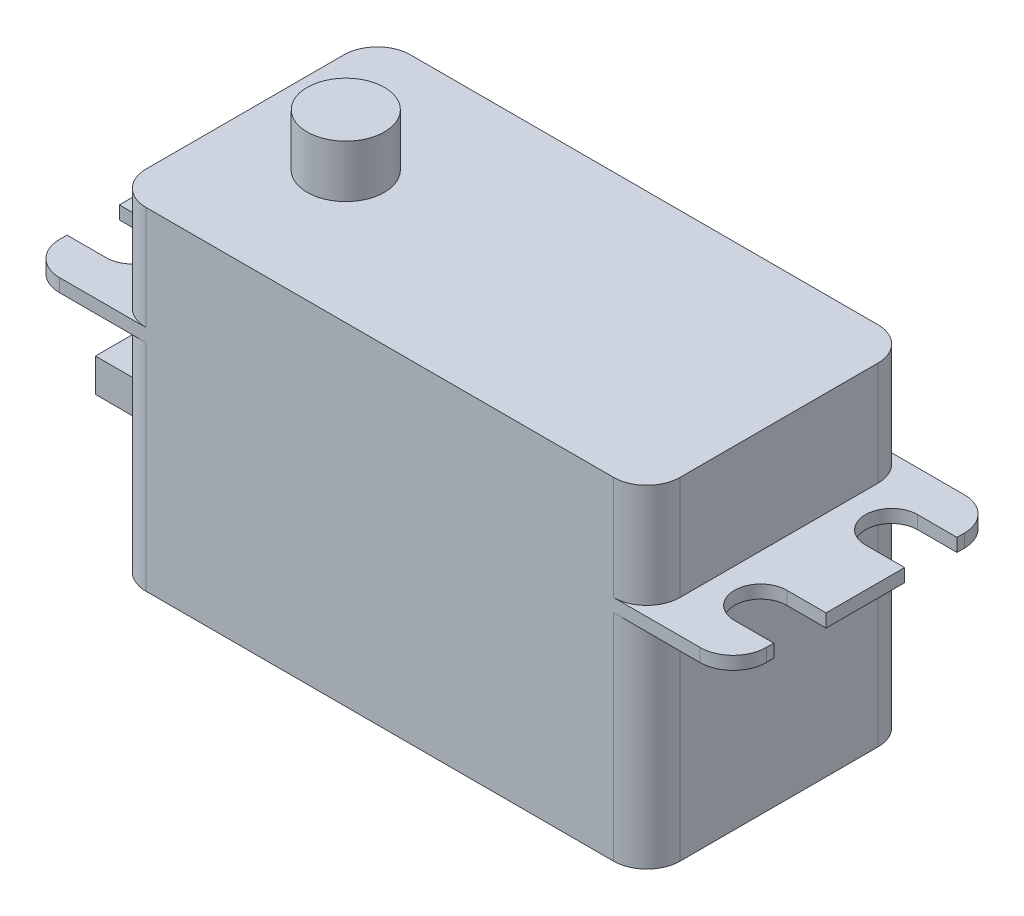
SolidWorks part; units mm, degrees
ref_plane "Front Plane" through (0, 0, 0) normal (0, 0, 1) x (1, 0, 0)
ref_plane "Top Plane" through (0, 0, 0) normal (0, 1, 0) x (1, 0, 0)
ref_plane "Right Plane" through (0, 0, 0) normal (1, 0, 0) x (0, 0, -1)
sketch "Sketch1" plane through (0, 0, 0) normal (0, 1, 0) x (1, 0, 0)
  line L0 (-16.17, 0) -> (16.17, 0) construction
  line L1 (-24.46, -10.1) -> (24.46, -10.1)
  line L2 (-27, -7.56) -> (-27, 7.56)
  line L3 (-24.46, 10.1) -> (24.46, 10.1)
  line L4 (27, -7.56) -> (27, 7.56)
  line L5 (-27, -10.1) -> (27, 10.1) construction
  line L6 (-27, 10.1) -> (27, -10.1) construction
  line L7 (0, -11.11) -> (0, 11.11) construction
  line L8 (24, 3) -> (27, 3)
  line L9 (24, 7) -> (27, 7)
  line L10 (27, 7) -> (27, 3)
  line L11 (24, -3) -> (27, -3)
  line L12 (24, -7) -> (27, -7)
  line L13 (27, -7) -> (27, -3)
  line L14 (-24, 7) -> (-27, 7)
  line L15 (-24, 3) -> (-27, 3)
  line L16 (-27, 3) -> (-27, 7)
  line L17 (-24, -7) -> (-27, -7)
  line L18 (-24, -3) -> (-27, -3)
  line L19 (-27, -3) -> (-27, -7)
  arc A0 (24, 7) -> (24, 3) centre (24, 5) ccw
  arc A1 (24, -7) -> (24, -3) centre (24, -5) cw
  arc A2 (-24, -7) -> (-24, -3) centre (-24, -5) ccw
  arc A3 (-24, 7) -> (-24, 3) centre (-24, 5) cw
  arc A4 (-24.46, -10.1) -> (-27, -7.56) centre (-24.46, -7.56) cw
  arc A5 (24.46, -10.1) -> (27, -7.56) centre (24.46, -7.56) ccw
  arc A6 (24.46, 10.1) -> (27, 7.56) centre (24.46, 7.56) cw
  arc A7 (-27, 7.56) -> (-24.46, 10.1) centre (-24.46, 7.56) cw
  point P0 (0, 0)
  dimension "D3" = 4
  dimension "D6" = 2.54
  dimension "D1" = 54
  dimension "D2" = 20.2
  dimension "D4" = 48
  dimension "D5" = 10
extrude "Boss-Extrude1" add sketch "Sketch1" along normal blind 1 contours A7 L2 L14 A3 L15 L18 A2 L17 A4 L1 A5 L4 L12 A1 L11 L8 A0 L9 A6 L3 region at (0, 0, 0)
sketch "Sketch3" plane through (0, 1, 0) normal (0, 1, 0) x (1, 0, 0)
  line L1 (-17.86, -10.1) -> (17.86, -10.1)
  line L2 (-20.4, -7.56) -> (-20.4, 7.56)
  line L3 (-17.86, 10.1) -> (17.86, 10.1)
  line L4 (20.4, -7.56) -> (20.4, 7.56)
  line L5 (-20.4, -10.1) -> (20.4, 10.1) construction
  line L6 (-20.4, 10.1) -> (20.4, -10.1) construction
  arc A0 (-17.86, -10.1) -> (-20.4, -7.56) centre (-17.86, -7.56) cw
  arc A1 (17.86, -10.1) -> (20.4, -7.56) centre (17.86, -7.56) ccw
  arc A2 (17.86, 10.1) -> (20.4, 7.56) centre (17.86, 7.56) cw
  arc A3 (-20.4, 7.56) -> (-17.86, 10.1) centre (-17.86, 7.56) cw
  point P0 (0, 0)
  dimension "D3" = 2.54
  dimension "D1" = 40.8
  dimension "D2" = 20.2
extrude "Boss-Extrude2" add sketch "Sketch3" along normal blind 7.95
sketch "Sketch4" plane through (0, 0, 0) normal (0, -1, 0) x (1, 0, 0)
  line L1 (-17.86, -10.1) -> (17.86, -10.1)
  line L2 (-20.4, -7.56) -> (-20.4, 7.56)
  line L3 (-17.86, 10.1) -> (17.86, 10.1)
  line L4 (20.4, -7.56) -> (20.4, 7.56)
  line L5 (-20.4, -10.1) -> (20.4, 10.1) construction
  line L6 (-20.4, 10.1) -> (20.4, -10.1) construction
  arc A0 (-17.86, -10.1) -> (-20.4, -7.56) centre (-17.86, -7.56) cw
  arc A1 (17.86, -10.1) -> (20.4, -7.56) centre (17.86, -7.56) ccw
  arc A2 (17.86, 10.1) -> (20.4, 7.56) centre (17.86, 7.56) cw
  arc A3 (-20.4, 7.56) -> (-17.86, 10.1) centre (-17.86, 7.56) cw
  point P0 (0, 0)
  dimension "D3" = 2.54
  dimension "D1" = 20.2
  dimension "D2" = 40.8
extrude "Boss-Extrude3" add sketch "Sketch4" along normal blind 16.45
sketch "Sketch5" plane through (-20.4, 0, 0) normal (-1, 0, 0) x (0, 0, 1)
  line L0 (-0.8843, -9.5287) -> (-0.8843, -11.2259)
  line L1 (-3.81, -11.6473) -> (3.81, -11.6473)
  line L2 (-3.81, -11.6473) -> (-3.81, -9.1073)
  line L3 (-3.81, -9.1073) -> (3.81, -9.1073)
  line L4 (3.81, -11.6473) -> (3.81, -9.1073)
  line L5 (-3.4243, -9.5287) -> (-1.6557, -9.5287)
  line L6 (-3.4243, -9.5287) -> (-3.4243, -11.2259)
  line L7 (-3.4243, -11.2259) -> (-1.6557, -11.2259)
  line L8 (-1.6557, -9.5287) -> (-1.6557, -11.2259)
  line L9 (-0.8843, -9.5287) -> (0.8843, -9.5287)
  line L10 (0.8843, -9.5287) -> (0.8843, -11.2259)
  line L11 (-0.8843, -11.2259) -> (0.8843, -11.2259)
  line L12 (1.6557, -9.5287) -> (1.6557, -11.2259)
  line L13 (1.6557, -9.5287) -> (3.4243, -9.5287)
  line L14 (3.4243, -9.5287) -> (3.4243, -11.2259)
  line L15 (1.6557, -11.2259) -> (3.4243, -11.2259)
  point P8 (0, -11.6473)
  point P18 (-3.4243, -10.3773)
  point P19 (-3.81, -10.3773)
  point P20 (0, -11.2259)
  dimension "D2" = 2.54
  dimension "D3" = 2.54
  dimension "D4" = 7.62
  dimension "D1" = 3
extrude "Boss-Extrude4" add sketch "Sketch5" along normal blind 7.62
sketch "Sketch6" plane through (0, 8.95, 0) normal (0, 1, 0) x (1, 0, 0)
  circle A0 centre (-12.7, 0) radius 2.95
  dimension "D1" = 5.9
  dimension "D2" = 12.7
extrude "Boss-Extrude5" add sketch "Sketch6" along normal blind 4
other "CPoint1" parameters "Diameter"=25.4, "StubLength"=38.1
ref_axis "Axis1" through (-38.02, -11.2259, -3.4243) along (1, 0, 0)
other "CPoint2" parameters "Diameter"=25.4, "StubLength"=38.1
ref_axis "Axis2" through (-38.02, -11.2259, -0.8843) along (1, 0, 0)
other "CPoint3" parameters "Diameter"=25.4, "StubLength"=38.1
ref_axis "Axis3" through (-38.02, -11.2259, 1.6557) along (1, 0, 0)
equation "\"Bodytube_OD\" = 6.17in"
equation "\"Bodytube_ID\" = 5.998in"
equation "\"Motor_OD\" = 4in"
equation "\"Fwd_Tube_Length\" = 40in"
equation "\"Mid_Tube_Length\" = 1in"
equation "\"Aft_Section_Length\"= 39in"
equation "\"AB_Coupler_OD_Length\"= 1in"
equation "\"AB_Coupling_Section_Length\"= 0.375in"
equation "\"AB_Coupler_Length\"= \"AB_Coupler_OD_Length\" + \"AB_Coupling_Section_Length\" * 2"
equation "\"Cutout_Angle\" = 80"
equation "\"AB_Paddle_Height\" = 0.375in"
equation "\"AB_Coupler_Num_Screws\"= 6"
equation "\"Num_Cutouts\" = 3"
equation "\"AB_Coupler_OD\"= 6.17in"
equation "\"AB_Coupler_ID\"= 5.75in"
equation "\"AB_Coupler_Surface_Diameter\"= 5.998in"
equation "\"AB_Coupling_Screw_Diameter\"= 0.1065in"
equation "\"AB_Central_Bushing_Length\" = .75in"
equation "\"Lead_Screw_Dist\" = 3.4in"
equation "\"Lead_Screw_Diam\" = 0.386in"
equation "\"Paddle_Pin_Offset\" = .25in"
equation "\"Paddle_Pin_Radius\" = 2.25in"
equation "\"Paddle_Gear_OD\" = 3.2in"
equation "\"Drive_Gear_OD\" = 1.7in"
equation "\"Fwd_BKHD_From_Top\" = 18in"
equation "\"Fin_Thickness\"= .118in"
equation "\"Guiderail_Cutout_Diameter\"= 1.5in"
equation "\"DB9_Hole_Dist\" = 25mm"
equation "\"Airbrakes_Wire_Hole_Dia\" = .25in"
equation "\"Airbrakes_Wire_Hole_Dist\" = 1.1in"
equation "\"Servo_Gear_Offset\" = 0.5in"
equation "\"D2@Sketch6\"=\"Servo_Gear_Offset\""
